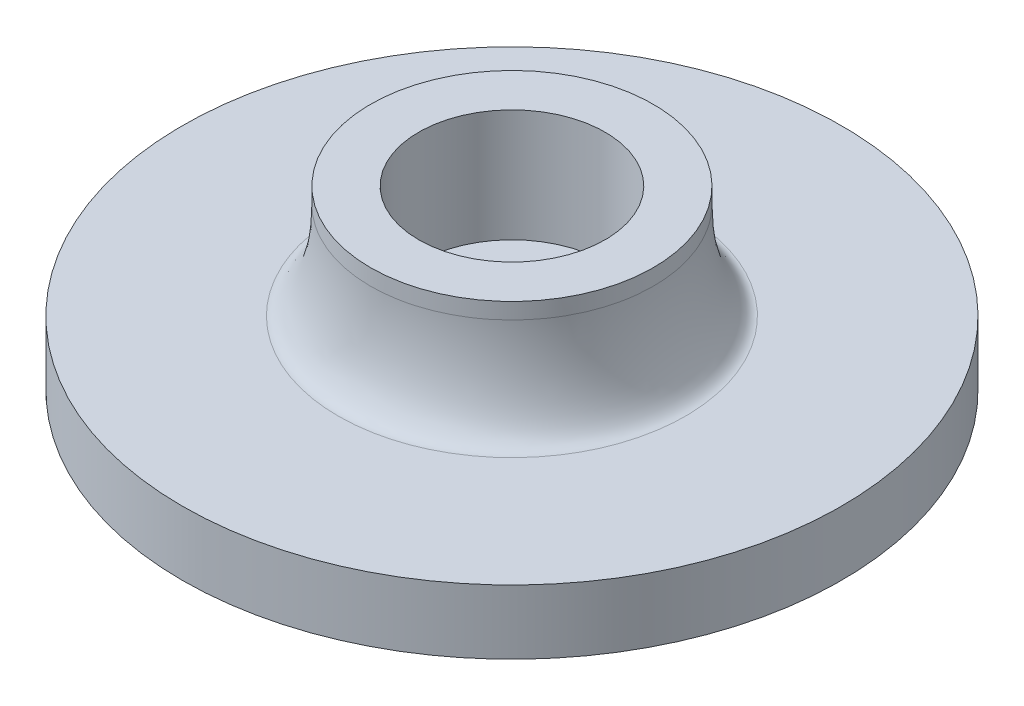
SolidWorks part; units mm, degrees
ref_plane "Front Plane" through (0, 0, 0) normal (0, 0, 1) x (1, 0, 0)
ref_plane "Top Plane" through (0, 0, 0) normal (0, 1, 0) x (1, 0, 0)
ref_plane "Right Plane" through (0, 0, 0) normal (1, 0, 0) x (0, 0, -1)
sketch "Sketch1" plane through (0, 0, 0) normal (0, 1, 0) x (1, 0, 0)
  circle A0 centre (0, 0) radius 10.25
  dimension "D1" = 20.5
extrude "Boss-Extrude1" add sketch "Sketch1" along normal blind 2
sketch "Sketch2" plane through (0, 2, 0) normal (0, 1, 0) x (1, 0, 0)
  circle A0 centre (0, 0) radius 2.9
  circle A1 centre (0, 0) radius 4.4
  dimension "D1" = 1.5
  dimension "D2" = 5.8
extrude "Boss-Extrude2" add sketch "Sketch2" along normal blind 3.5
fillet "Fillet1" radius 1 1 edges at (0, 2, 4.4) second distance 3 first distance on face at (0, 2, 4.4)
sketch "Sketch3" plane through (0, 0, 0) normal (0, -1, 0) x (1, 0, 0)
  circle A0 centre (0, 0) radius 1.5
  dimension "D1" = 3
extrude "Cut-Extrude1" cut sketch "Sketch3" against normal up to surface (2 mm away) up to face at (0, 2, 2.9)
